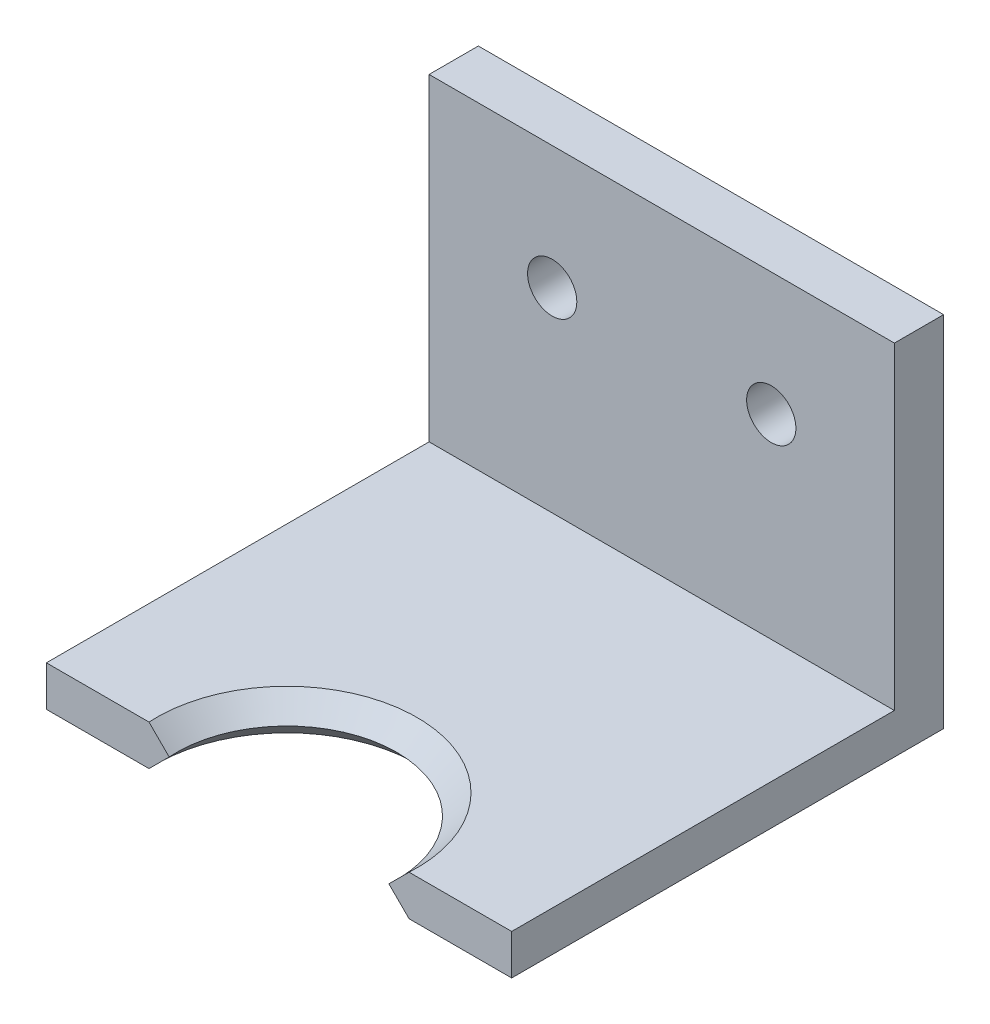
SolidWorks part; units mm, degrees
ref_plane "Front Plane" through (0, 0, 0) normal (0, 0, 1) x (1, 0, 0)
ref_plane "Top Plane" through (0, 0, 0) normal (0, 1, 0) x (1, 0, 0)
ref_plane "Right Plane" through (0, 0, 0) normal (1, 0, 0) x (0, 0, -1)
sketch "Profile-Sketch1" plane through (0, 0, 0) normal (1, 0, 0) x (0, 0, -1)
  line L0 (0, 0) -> (24.675, 0)
  line L1 (24.675, 0) -> (24.675, 20.5151)
  line L2 (24.675, 20.5151) -> (27.85, 20.5151)
  line L3 (27.85, 20.5151) -> (27.85, -2.6)
  line L4 (27.85, -2.6) -> (0, -2.6)
  line L5 (0, -2.6) -> (0, 0)
  dimension "D1" = 3.175
  dimension "D2" = 27.85
  dimension "D3" = 23.1151
  dimension "D4" = 2.6
extrude "Profile-Boss-Extrude1" add sketch "Profile-Sketch1" along normal blind 30
sketch "CollarSketch2" plane through (0, 0, 0) normal (0, 1, 0) x (1, 0, 0)
  line L0 (30, 0) -> (0, 0) construction
  line L1 (0, 24.675) -> (0, 0) construction
  line L2 (7.9176, 0) -> (22.0824, 0)
  arc A0 (22.0824, 0) -> (7.9176, 0) centre (15, 0.5) ccw
  dimension "D1" = 14.2
  dimension "D2" = 0.5
  dimension "D3" = 15
extrude "CollarCut-Extrude1" cut sketch "CollarSketch2" against normal through all
chamfer "Collar-Chamfer2" distance 1.3 angle 45 2 edges at (15, -2.6, -7.6) (15, 0, -7.6)
sketch "MountingHoles-Sketch3" plane through (0, 0, -24.675) normal (0, 0, 1) x (1, 0, 0)
  line L0 (30, 20.5151) -> (0, 20.5151) construction
  line L1 (30, 20.5151) -> (30, 0) construction
  line L2 (0, 20.5151) -> (0, 0) construction
  circle A12 centre (7.9375, 12.5776) radius 1.5875
  circle A13 centre (22.0625, 12.5776) radius 1.5875
  dimension "D4" = 3.175
  dimension "D1" = 7.9375
  dimension "D2" = 7.9375
  dimension "D3" = 7.9375
extrude "MountingHoles-Cut-Extrude2" cut sketch "MountingHoles-Sketch3" against normal through all
equation "\"RailThickness\"= .125in'Spec"
equation "\"D1@Profile-Sketch1\"=\"RailThickness\""
equation "\"LM8UUCollarDiameter\"= 14.2mm"
equation "\"LM8UUDiameter\"= 15mm"
equation "\"MidSideRailHeight\"= 1.25in"
equation "\"RodStabilizerWidth\"= \"StepperMountingHoleOffsetFromLeftOrRightSide\" + \"StepperMountingHoleDistance\" / 2 + \"RailThickness\" - \"RodStabilizerCollarOffset\" + 1mm"
equation "\"RodStabilizerDepth\"= \"LM8UUDiameter\" * 2"
equation "\"D2@Profile-Sketch1\" = \"RodStabilizerWidth\""
equation "\"D3@Profile-Sketch1\" = \"RodStabilizerLength\""
equation "\"D1@Profile-Boss-Extrude1\" = \"RodStabilizerDepth\""
equation "\"D1@CollarSketch2\" = \"LM8UUCollarDiameter\""
equation "\"D3@CollarSketch2\" = \"RodStabilizerDepth\" / 2"
equation "\"HoleOffsetFromEdge\"= \"RailThickness\" * 2.5"
equation "\"StepperMountingHoleOffsetFromItsSide\"= 5.5mm'Spec"
equation "\"StepperMountingHoleOffsetFromLeftOrRightSide\"= \"StepperMountingHoleOffsetFromItsSide\" + \"RailThickness\""
equation "\"StepperMountingHoleDistance\"= 31mm'Spec"
equation "\"RodStabilizerCollarOffset\"= 0.5mm"
equation "\"D2@CollarSketch2\"=\"RodStabilizerCollarOffset\""
equation "\"LM8UUHeight\"= 24mm'Spec"
equation "\"ZAxisLeadScrewLength\"= 200mm"
equation "\"LM8UUEndToStartOfCollar\"= 2.5mm"
equation "\"LegHeight\"= 70mm'Space needed for PSU/Stepper/Electronics"
equation "\"V1 BottomOfLowerRail\"= \"LegHeight\""
equation "\"LM8UUCollarWidth\"= 1.3mm"
equation "\"StepperShaftLength\"= 24mm'Pulley will be attached to the end"
equation "\"V2 ToBedAtTopOfZAxis\" = \"V1 BottomOfLowerRail\" - \"LowerEnclosureThickness\" + \"StepperShaftLength\" + \"ZAxisLeadScrewLength\" - \"LM8UUHeight\" / 2"
equation "\"HotEndToTopOfXAxisGB\"= 63.315144mm'Measured from the100.Should be 63.315144"
equation "\"TopOfGBToBottomOfLinearRail\"= \"LinearGBWidth\" / 2 + \"LinearRailWidth\" / 2"
equation "\"LinearGBWidth\"= 27mm'Spec"
equation "\"V5 ToBottomOfXAxisLinearRail\"= \"V4 ToTopOfBuildPlate/HotEndTip\" + \"HotEndToTopOfXAxisGB\" - \"TopOfGBToBottomOfLinearRail\""
equation "\"LinearRailWidth\"= 12mm'Spec"
equation "\"V6 ToBottomOfGantryPulley\"= \"V5 ToBottomOfXAxisLinearRail\" - \"DistanceFromGABTopToLowerPulley\""
equation "\"GABUpperHeight\"= 6mm"
equation "\"GABMidWallHeight\"= 28mm'Must equal 28 or changes alignment"
equation "\"20TGT2PulleyWidth\"= 8.7mm'The STL of the Pulley in the diagram is a bit larger"
equation "\"GABMidShortRiserHeight\"= \"GABMidWallHeight\" / 2 - \"20TGT2PulleyWidth\"'Equals 5.3"
equation "\"GABRiserBossOffset\"= 0.8mm'Aligns Pulleys"
equation "\"DistanceFromGABTopToLowerPulley\"= \"GABUpperHeight\" + \"GABMidWallHeight\" - \"GABMidShortRiserHeight\" + \"GABRiserBossOffset\" / 2"
equation "\"V7 ToTopOfMidBackRail\"= \"V6 ToBottomOfGantryPulley\" + \"StepperShaftLength\""
equation "\"BedToBuildPlateStandoffLength\"= 15mm"
equation "\"BuildPlateHeight\"= 8mm'Spec"
equation "\"V4 ToTopOfBuildPlate/HotEndTip\"= \"V2 ToBedAtTopOfZAxis\" + \"BedToBuildPlateStandoffLength\" + \"BuildPlateHeight\""
equation "\"D1@MountingHoles-Sketch3\"=\"HoleOffsetFromEdge\""
equation "\"D2@MountingHoles-Sketch3\"=\"HoleOffsetFromEdge\""
equation "\"D3@MountingHoles-Sketch3\"=\"HoleOffsetFromEdge\""
equation "\"FasteningHoleDiameter\"= .125in"
equation "\"D4@MountingHoles-Sketch3\"=\"FasteningHoleDiameter\""
equation "\"D4@Profile-Sketch1\"=\"LM8UUCollarWidth\"*2"
equation "\"RodStabilizerLength\"= \"V7 ToTopOfMidBackRail\" - \"RailThickness\" - \"MidSideRailHeight\" - \"V2 ToBedAtTopOfZAxis\" - \"LM8UUHeight\" + \"HoleOffsetFromEdge\" * 2 + \"LM8UUEndToStartOfCollar\" + \"LM8UUCollarWidth\" / 2 + \"LM8UUCollarWidth\"'Equals 23.11514"
equation "\"D1@Collar-Chamfer2\"=\"LM8UUCollarWidth\""
equation "\"LowerEnclosureThickness\"= 5mm"
